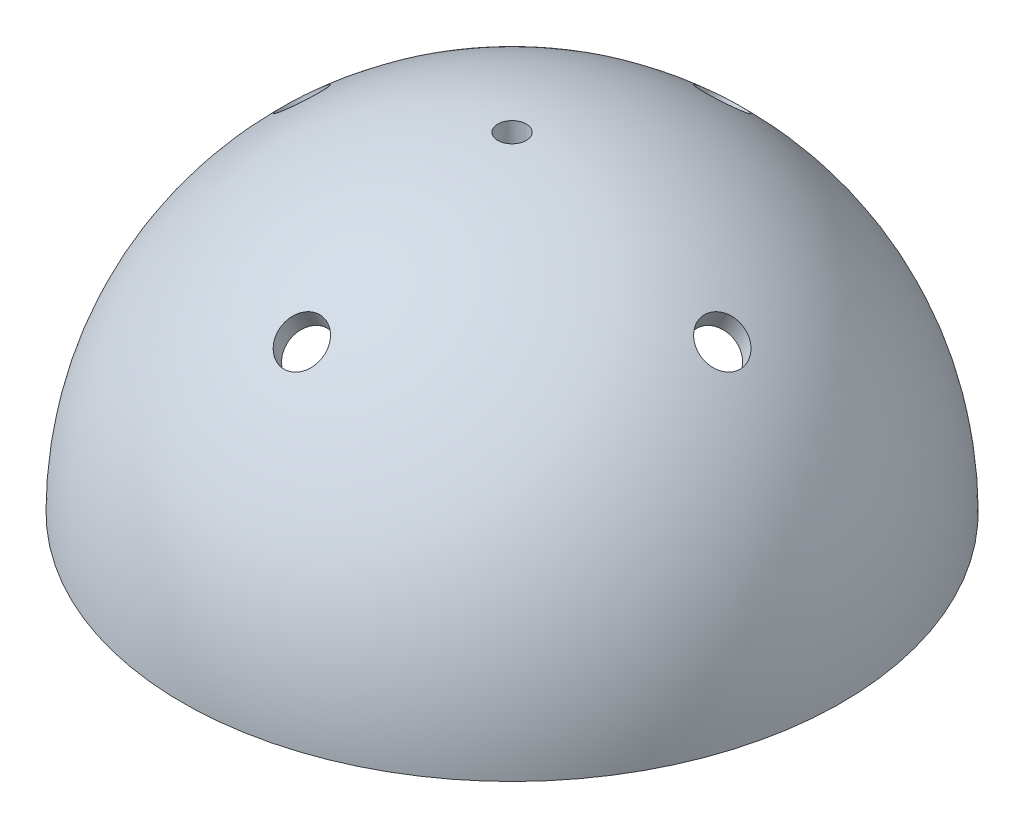
SolidWorks part; units mm, degrees
ref_plane "Front Plane" through (0, 0, 0) normal (0, 0, 1) x (1, 0, 0)
ref_plane "Top Plane" through (0, 0, 0) normal (0, 1, 0) x (1, 0, 0)
ref_plane "Right Plane" through (0, 0, 0) normal (1, 0, 0) x (0, 0, -1)
sketch "Sketch1" plane through (0, 0, 0) normal (0, 0, 1) x (1, 0, 0)
  line L0 (0, 0) -> (0, 40.2918)
  line L1 (-40.2918, 0) -> (0, 0)
  arc A0 (0, 40.2918) -> (-40.2918, 0) centre (0, 0) ccw
revolve "Revolve2" add sketch "Sketch1" angle 360 about L0
sketch "Sketch3" plane through (0, 0, 0) normal (0, 0, 1) x (1, 0, 0)
  line L0 (0, 0) -> (0, 38.0661)
  line L1 (0, 0) -> (-38.0909, 0)
  line L2 (-40.2918, 0) -> (40.2918, 0) construction
  line L3 (-0.0124, -0.0124) -> (-6.3781, 0)
  line L4 (-6.3781, 0) -> (-6.3781, 37.5303)
  line L5 (-0.0124, -0.0124) -> (-0.0124, -20.1145)
  line L6 (-27.134, 33.79) -> (-0.0124, -19.5265)
  line L7 (-0.0124, -20.1145) -> (-13.5732, 7.1317)
  line L8 (-13.5732, 7.1317) -> (-11.3492, 8.2386)
  line L9 (-11.3492, 8.2386) -> (-25.9281, 37.5303)
  line L10 (-13.5732, 7.1317) -> (-29.0891, 37.5303)
  line L11 (-29.0891, 37.5303) -> (-25.9281, 37.5303)
  arc A0 (0, 38.0661) -> (-38.0909, 0) centre (-0.0124, -0.0124) ccw
  arc A1 (0, 40.2918) -> (-27.134, 33.79) centre (-0.0124, -19.5265) ccw
  arc A2 (40.2918, 0) -> (-40.2918, 0) centre (0, 0) ccw construction
revolve "Cut-Revolve1" cut sketch "Sketch3" angle 360 about L10
ref_axis "Axis1" through (-44.321, 0, 0) along (1, 0, 0)
ref_axis "Axis2" through (0, 42.3064, 0) along (0, -1, 0)
pattern_circular "CirPattern1" count 4 every 90 about axis through (0, 42.3064, 0) along (0, -1, 0) of "Cut-Revolve1"
sketch "Sketch4" plane through (0, 0, 0) normal (0, 0, 1) x (1, 0, 0)
  line L0 (-6.4179, 0) -> (-6.6203, 0)
  line L1 (-44.321, 0) -> (44.321, 0) construction
  line L2 (-38.3627, 0) -> (-6.4179, 0)
  line L3 (0, 0) -> (0, 38.0244)
  line L4 (0, 42.3064) -> (0, -2.0146) construction
  line L5 (0, 38.0244) -> (0, 33.1652)
  line L6 (0, 33.1652) -> (0, 0)
  line L7 (-6.6203, 3.6819) -> (-6.6203, 4.5103)
  line L8 (-6.6203, 0) -> (-6.6203, 37.4761)
  line L9 (-6.6203, 37.4761) -> (-6.6203, 0.8921)
  line L10 (-6.6203, 4.5103) -> (-6.6203, 8.6477)
  line L11 (-6.4179, 0) -> (-6.6203, 37.4761)
  arc A1 (-6.6203, 37.4761) -> (-38.3627, 0) centre (-0.1691, -0.1691) ccw
revolve "Cut-Revolve2" cut sketch "Sketch4" angle 360 about L3 region at (-19.9016, 15.3716, 0)
sketch "Sketch5" plane through (0, 0, 0) normal (0, 0, 1) x (1, 0, 0)
  line L0 (0, 0) -> (0, 48.2932)
  line L1 (0, 42.3064) -> (0, -2.0146) construction
  line L2 (0, 48.2932) -> (1.742, 48.2932)
  line L3 (1.742, 48.2932) -> (1.742, -4.609)
  line L4 (1.742, -4.609) -> (0, -4.609)
  line L5 (0, -4.609) -> (0, 0)
revolve "Cut-Revolve3" cut sketch "Sketch5" angle 360 about axis through (0, 42.3064, 0) along (0, -1, 0)
